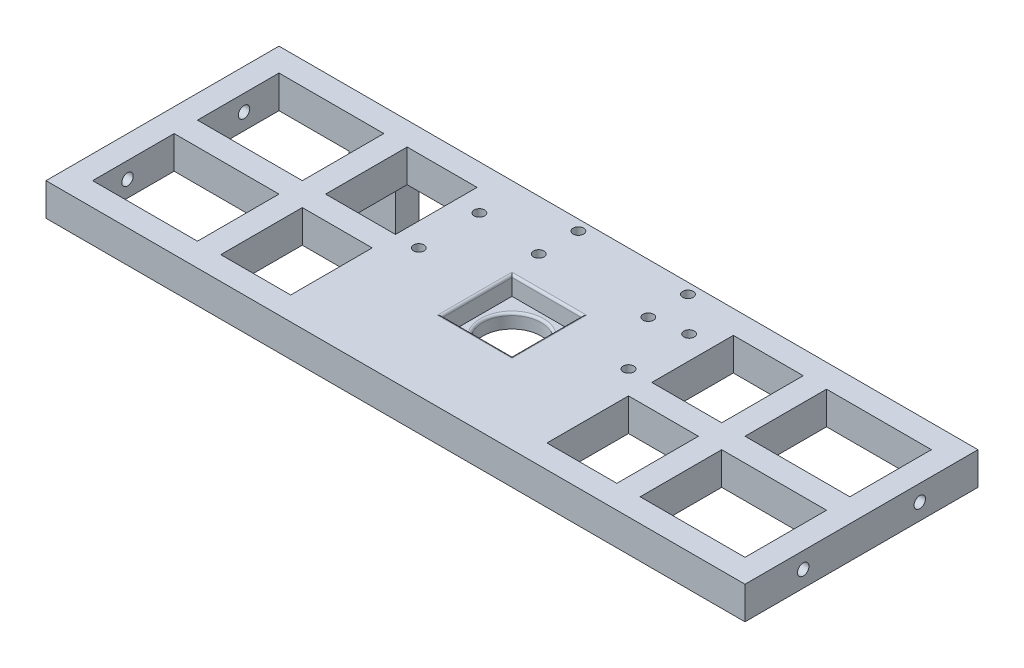
SolidWorks part; units mm, degrees
ref_plane "前视基准面" through (0, 0, 0) normal (0, 0, 1) x (1, 0, 0)
ref_plane "上视基准面" through (0, 0, 0) normal (0, 1, 0) x (1, 0, 0)
ref_plane "右视基准面" through (0, 0, 0) normal (1, 0, 0) x (0, 0, -1)
sketch "草图1" plane through (0, 0, 0) normal (0, 1, 0) x (1, 0, 0)
  line L1 (0, 0) -> (-300, 0)
  line L2 (0, 0) -> (0, 100)
  line L3 (0, 100) -> (-300, 100)
  line L4 (-300, 0) -> (-300, 100)
  dimension "D1" = 300
  dimension "D2" = 100
extrude "凸台-拉伸1" add sketch "草图1" along normal blind 16
sketch "草图2" plane through (0, 16, 0) normal (0, 1, 0) x (1, 0, 0)
  line L0 (-150, 100) -> (-150, 50) construction
  line L1 (0, 100) -> (-300, 100) construction
  line L2 (-300, 50) -> (-150, 50) construction
  line L3 (-300, 100) -> (-300, 0) construction
  line L5 (-165, 65) -> (-135, 65)
  line L6 (-165, 65) -> (-165, 35)
  line L7 (-165, 35) -> (-135, 35)
  line L8 (-135, 65) -> (-135, 35)
  line L9 (-165, 65) -> (-135, 35) construction
  line L10 (-165, 35) -> (-135, 65) construction
  dimension "D1" = 50
  dimension "D2" = 30
  dimension "D3" = 30
extrude "切除-拉伸1" cut sketch "草图2" against normal blind 8
sketch "草图3" plane through (0, 8, 0) normal (0, 1, 0) x (1, 0, 0)
  line L0 (-135, 65) -> (-165, 65) construction
  line L1 (-135, 35) -> (-135, 65) construction
  circle A0 centre (-150, 50) radius 12.5
  dimension "D3" = 25
  dimension "D1" = 15
  dimension "D2" = 15
extrude "切除-拉伸2" cut sketch "草图3" against normal blind 14
sketch "草图4" plane through (0, 16, 0) normal (0, 1, 0) x (1, 0, 0)
  line L0 (-165, 65) -> (-165, 35) construction
  line L1 (-295, 90) -> (-245, 90)
  line L2 (-295, 90) -> (-295, 55)
  line L3 (-295, 55) -> (-245, 55)
  line L4 (-245, 90) -> (-245, 55)
  line L5 (-295, 45) -> (-245, 45)
  line L6 (-295, 45) -> (-295, 10)
  line L7 (-295, 10) -> (-245, 10)
  line L8 (-245, 45) -> (-245, 10)
  line L9 (-235, 90) -> (-185, 90)
  line L10 (-235, 90) -> (-235, 55)
  line L11 (-235, 55) -> (-185, 55)
  line L12 (-185, 90) -> (-185, 55)
  line L13 (-235, 45) -> (-185, 45)
  line L14 (-235, 45) -> (-235, 10)
  line L15 (-235, 10) -> (-185, 10)
  line L16 (-185, 45) -> (-185, 10)
  line L17 (0, 100) -> (-300, 100) construction
  line L18 (-300, 0) -> (0, 0) construction
  line L19 (-300, 100) -> (-300, 0) construction
  line L20 (-150, 100) -> (-150, 73.2626) construction
  line L21 (-5, 10) -> (-55, 10)
  line L22 (-55, 45) -> (-55, 10)
  line L23 (-5, 45) -> (-55, 45)
  line L24 (-5, 45) -> (-5, 10)
  line L25 (-65, 10) -> (-115, 10)
  line L26 (-115, 45) -> (-115, 10)
  line L27 (-65, 45) -> (-115, 45)
  line L28 (-65, 45) -> (-65, 10)
  line L29 (-65, 55) -> (-115, 55)
  line L30 (-115, 90) -> (-115, 55)
  line L31 (-65, 90) -> (-115, 90)
  line L32 (-65, 90) -> (-65, 55)
  line L33 (-5, 55) -> (-55, 55)
  line L34 (-55, 90) -> (-55, 55)
  line L35 (-5, 90) -> (-55, 90)
  line L36 (-5, 90) -> (-5, 55)
  dimension "D1" = 20
  dimension "D2" = 20
  dimension "D3" = 10
  dimension "D4" = 10
  dimension "D5" = 10
  dimension "D6" = 35
  dimension "D7" = 10
  dimension "D8" = 10
  dimension "D9" = 5
  dimension "D10" = 5
  dimension "D11" = 35
  dimension "D12" = 35
  dimension "D13" = 50
  dimension "D14" = 50
  dimension "D15" = 50
  dimension "D16" = 50
extrude "切除-拉伸3" cut sketch "草图4" against normal up to next
sketch "草图7" plane through (-185, 0, 0) normal (-1, 0, 0) x (0, 0, 1)
  line L0 (-45, 0) -> (-10, 0) construction
  line L1 (-10, 0) -> (-10, 16) construction
  line L2 (-10, 16) -> (-45, 16) construction
  line L3 (-45, 16) -> (-45, 0) construction
  line L4 (-90, 0) -> (-55, 0) construction
  line L5 (-55, 0) -> (-55, 16) construction
  line L6 (-55, 16) -> (-90, 16) construction
  line L7 (-90, 16) -> (-90, 0) construction
  line L8 (-45, 0) -> (-10, 0)
  line L9 (-10, 0) -> (-10, 16)
  line L10 (-10, 16) -> (-45, 16)
  line L11 (-45, 16) -> (-45, 0)
  line L12 (-90, 0) -> (-55, 0)
  line L13 (-55, 0) -> (-55, 16)
  line L14 (-55, 16) -> (-90, 16)
  line L15 (-90, 16) -> (-90, 0)
extrude "凸台-拉伸2" add sketch "草图7" along normal blind 20
sketch "草图8" plane through (-115, 0, 0) normal (1, 0, 0) x (0, 0, -1)
  line L0 (10, 0) -> (45, 0) construction
  line L1 (45, 0) -> (45, 16) construction
  line L2 (45, 16) -> (10, 16) construction
  line L3 (10, 16) -> (10, 0) construction
  line L4 (55, 0) -> (90, 0) construction
  line L5 (90, 0) -> (90, 16) construction
  line L6 (90, 16) -> (55, 16) construction
  line L7 (55, 16) -> (55, 0) construction
  line L8 (10, 0) -> (45, 0)
  line L9 (45, 0) -> (45, 16)
  line L10 (45, 16) -> (10, 16)
  line L11 (10, 16) -> (10, 0)
  line L12 (55, 0) -> (90, 0)
  line L13 (90, 0) -> (90, 16)
  line L14 (90, 16) -> (55, 16)
  line L15 (55, 16) -> (55, 0)
extrude "凸台-拉伸3" add sketch "草图8" along normal blind 20
sketch "草图9" plane through (0, 0, 0) normal (0, -1, 0) x (1, 0, 0)
  line L5 (-295, -90) -> (-245, -90) construction
  line L10 (-260, -90) -> (-240, -90)
  line L20 (-260, -90) -> (-260, -100)
  line L21 (-260, -100) -> (-240, -100)
  line L22 (-240, -90) -> (-240, -100)
  line L23 (0, -100) -> (-300, -100) construction
  line L24 (-300, -100) -> (-300, 0) construction
  dimension "D3" = 20
  dimension "D4" = 40
extrude "凸台-拉伸4" add sketch "草图9" along normal blind 25
fillet "圆角1" radius 1 1 edges at (-150, 8, -37.5)
fillet "圆角2" radius 1 4 edges at (-135, 16, -50) (-150, 16, -65) (-150, 16, -35) (-165, 16, -50)
sketch "草图13" plane through (-5, 0, 0) normal (-1, 0, 0) x (0, 0, 1)
  line L0 (-90, 0) -> (-55, 0) construction
  line L1 (-55, 0) -> (-55, 16) construction
  line L2 (-55, 16) -> (-90, 16) construction
  line L3 (-90, 16) -> (-90, 0) construction
  line L4 (-45, 0) -> (-10, 0) construction
  line L5 (-10, 0) -> (-10, 16) construction
  line L6 (-10, 16) -> (-45, 16) construction
  line L7 (-45, 16) -> (-45, 0) construction
  line L8 (-90, 0) -> (-55, 0)
  line L9 (-55, 0) -> (-55, 16)
  line L10 (-55, 16) -> (-90, 16)
  line L11 (-90, 16) -> (-90, 0)
  line L12 (-45, 0) -> (-10, 0)
  line L13 (-10, 0) -> (-10, 16)
  line L14 (-10, 16) -> (-45, 16)
  line L15 (-45, 16) -> (-45, 0)
extrude "凸台-拉伸6" add sketch "草图13" along normal blind 4
sketch "草图14" plane through (-295, 0, 0) normal (1, 0, 0) x (0, 0, -1)
  line L0 (55, 0) -> (90, 0) construction
  line L1 (90, 0) -> (90, 16) construction
  line L2 (90, 16) -> (55, 16) construction
  line L3 (55, 16) -> (55, 0) construction
  line L4 (10, 0) -> (45, 0) construction
  line L5 (45, 0) -> (45, 16) construction
  line L6 (45, 16) -> (10, 16) construction
  line L7 (10, 16) -> (10, 0) construction
  line L8 (55, 0) -> (90, 0)
  line L9 (90, 0) -> (90, 16)
  line L10 (90, 16) -> (55, 16)
  line L11 (55, 16) -> (55, 0)
  line L12 (10, 0) -> (45, 0)
  line L13 (45, 0) -> (45, 16)
  line L14 (45, 16) -> (10, 16)
  line L15 (10, 16) -> (10, 0)
extrude "凸台-拉伸7" add sketch "草图14" along normal blind 4
sketch "草图17" plane through (-291, 0, 0) normal (1, 0, 0) x (0, 0, -1)
  line L0 (10, 16) -> (10, 0) construction
  line L1 (10, 0) -> (45, 0) construction
  line L2 (45, 0) -> (45, 16) construction
  line L3 (45, 16) -> (10, 16) construction
  line L4 (55, 16) -> (55, 0) construction
  line L5 (55, 0) -> (90, 0) construction
  line L6 (90, 0) -> (90, 16) construction
  line L7 (90, 16) -> (55, 16) construction
  line L8 (10, 16) -> (10, 0)
  line L9 (10, 0) -> (45, 0)
  line L10 (45, 0) -> (45, 16)
  line L11 (45, 16) -> (10, 16)
  line L12 (55, 16) -> (55, 0)
  line L13 (55, 0) -> (90, 0)
  line L14 (90, 0) -> (90, 16)
  line L15 (90, 16) -> (55, 16)
extrude "凸台-拉伸8" add sketch "草图17" along normal blind 1
sketch "草图18" plane through (-9, 0, 0) normal (-1, 0, 0) x (0, 0, 1)
  line L0 (-45, 16) -> (-45, 0) construction
  line L1 (-45, 0) -> (-10, 0) construction
  line L2 (-10, 0) -> (-10, 16) construction
  line L3 (-10, 16) -> (-45, 16) construction
  line L4 (-90, 16) -> (-90, 0) construction
  line L5 (-90, 0) -> (-55, 0) construction
  line L6 (-55, 0) -> (-55, 16) construction
  line L7 (-55, 16) -> (-90, 16) construction
  line L8 (-45, 16) -> (-45, 0)
  line L9 (-45, 0) -> (-10, 0)
  line L10 (-10, 0) -> (-10, 16)
  line L11 (-10, 16) -> (-45, 16)
  line L12 (-90, 16) -> (-90, 0)
  line L13 (-90, 0) -> (-55, 0)
  line L14 (-55, 0) -> (-55, 16)
  line L15 (-55, 16) -> (-90, 16)
extrude "凸台-拉伸9" add sketch "草图18" along normal blind 1
sketch "草图24" [suppressed] plane through (0, 16, 0) normal (0, 1, 0) x (1, 0, 0)
  circle A0 centre (-195, 81) radius 2.25
  circle A1 centre (-205, 54.9815) radius 2.25
  circle A2 centre (-105, 81) radius 2.25
  circle A3 centre (-115, 54.9815) radius 2.25
  dimension "D1" = 4.5
  dimension "D2" = 4.5
  dimension "D3" = 4.5
  dimension "D4" = 4.5
extrude "切除-拉伸13" [suppressed] cut sketch "草图24" against normal blind 5
sketch "草图26" plane through (0, 0, 0) normal (0, -1, 0) x (1, 0, 0)
  line L12 (-260, -90) -> (-290, -90)
  line L13 (-290, -90) -> (-290, -55)
  line L14 (-290, -55) -> (-245, -55)
  line L15 (-245, -55) -> (-245, -90)
  line L16 (-245, -90) -> (-240, -90)
  line L17 (-240, -90) -> (-240, -100)
  line L18 (-240, -100) -> (0, -100)
  line L19 (0, -100) -> (0, 0)
  line L20 (0, 0) -> (-300, 0)
  line L21 (-300, 0) -> (-300, -100)
  line L22 (-300, -100) -> (-260, -100)
  line L23 (-260, -100) -> (-260, -90)
  line L24 (-260, -90) -> (-290, -90)
  line L25 (-290, -90) -> (-290, -55)
  line L26 (-290, -55) -> (-245, -55)
  line L27 (-245, -55) -> (-245, -90)
  line L28 (-245, -90) -> (-240, -90)
  line L29 (-240, -90) -> (-240, -100)
  line L30 (-240, -100) -> (0, -100)
  line L31 (0, -100) -> (0, 0)
  line L32 (0, 0) -> (-300, 0)
  line L33 (-300, 0) -> (-300, -100)
  line L34 (-300, -100) -> (-260, -100)
  line L35 (-260, -100) -> (-260, -90)
  dimension "D1" = 0
extrude "切除-拉伸15" cut sketch "草图26" against normal blind 2
sketch "草图28" plane through (0, 16, 0) normal (0, 1, 0) x (1, 0, 0)
  line L0 (-205, 55) -> (-205, 90) construction
  line L1 (0, 100) -> (-300, 100) construction
  line L2 (-95, 90) -> (-95, 55) construction
  circle A8 centre (-105.0028, 55) radius 2.25
  circle A9 centre (-105, 81) radius 2.25
  circle A10 centre (-120, 78.5) radius 2.25
  circle A11 centre (-120, 95.5) radius 2.25
  circle A12 centre (-167.0001, 78.5) radius 2.25
  circle A13 centre (-167.0001, 95.5) radius 2.25
  circle A14 centre (-195, 55) radius 2.25
  circle A15 centre (-195, 81) radius 2.25
  dimension "D1" = 10
  dimension "D2" = 10
  dimension "D3" = 26
  dimension "D4" = 19
  dimension "D5" = 4.5
  dimension "D6" = 4.5
  dimension "D7" = 17
  dimension "D8" = 4.5
  dimension "D9" = 4.5
  dimension "D10" = 17
  dimension "D11" = 47.0001
  dimension "D12" = 47.0001
  dimension "D13" = 4.5
  dimension "D14" = 4.5
  dimension "D15" = 4.5
  dimension "D16" = 4.5
  dimension "D17" = 25
  dimension "D18" = 25
  dimension "D19" = 10
  dimension "D20" = 10.0028
  dimension "D21" = 26
  dimension "D22" = 19
  dimension "D23" = 4.5
  dimension "D24" = 4.5
extrude "切除-拉伸18" cut sketch "草图28" against normal blind 5
sketch "草图30" plane through (0, 11, 0) normal (0, 1, 0) x (1, 0, 0)
  circle A2 centre (-195, 81) radius 1.5
  circle A3 centre (-195, 55) radius 1.5
  circle A4 centre (-167.0001, 95.5) radius 1.5
  circle A5 centre (-167.0001, 78.5) radius 1.5
  circle A6 centre (-120, 95.5) radius 1.5
  circle A7 centre (-120, 78.5) radius 1.5
  circle A8 centre (-105, 81) radius 1.5
  circle A9 centre (-105.0028, 55) radius 1.5
  dimension "D1" = 3
extrude "切除-拉伸20" cut sketch "草图30" against normal blind 4
sketch "草图33" plane through (-300, 0, 0) normal (-1, 0, 0) x (0, 0, 1)
  line L0 (-100, 16) -> (0, 16) construction
  line L3 (-100, 16) -> (-100, 2) construction
  line L4 (0, 16) -> (0, 2) construction
  circle A0 centre (-75, 9) radius 2.45
  circle A1 centre (-25, 9) radius 2.45
  dimension "D1" = 7
  dimension "D2" = 7
  dimension "D3" = 4.9
  dimension "D4" = 4.9
  dimension "D5" = 25
  dimension "D6" = 25
extrude "切除-拉伸22" cut sketch "草图33" against normal blind 13.2
sketch "草图34" plane through (0, 0, 0) normal (1, 0, 0) x (0, 0, -1)
  circle A0 centre (75, 9) radius 2.45 construction
  circle A1 centre (25, 9) radius 2.45 construction
  circle A2 centre (75, 9) radius 2.45
  circle A3 centre (25, 9) radius 2.45
extrude "切除-拉伸23" cut sketch "草图34" against normal blind 13.2
